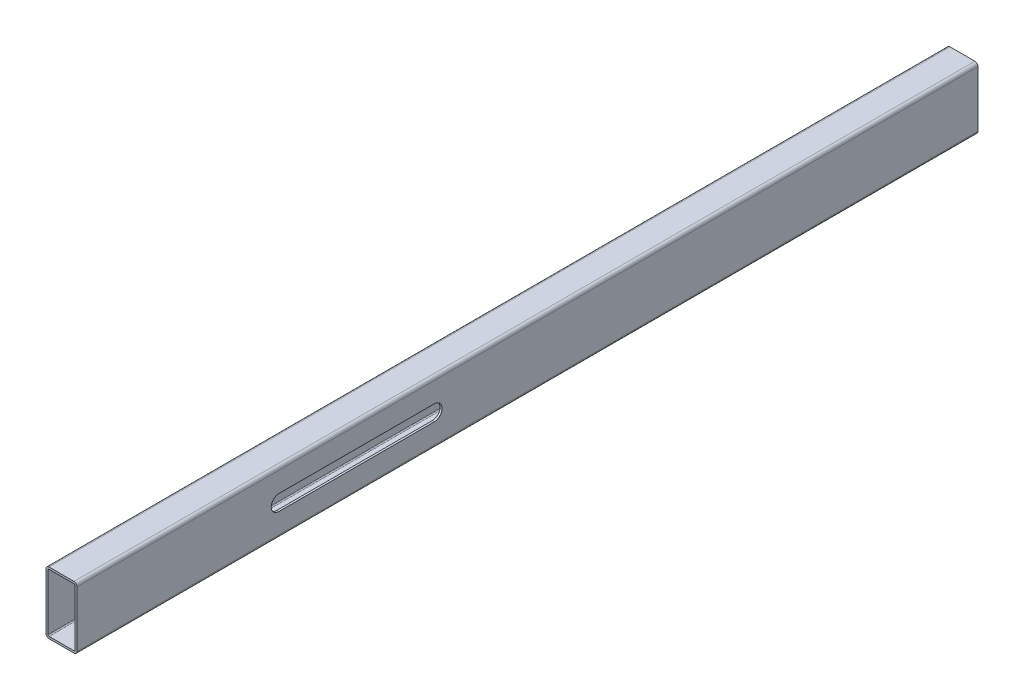
SolidWorks part; units mm, degrees
ref_plane "Front Plane" through (0, 0, 0) normal (0, 0, 1) x (1, 0, 0)
ref_plane "Top Plane" through (0, 0, 0) normal (0, 1, 0) x (1, 0, 0)
ref_plane "Right Plane" through (0, 0, 0) normal (1, 0, 0) x (0, 0, -1)
sketch "Sketch1" plane through (0, 0, 0) normal (0, 0, 1) x (1, 0, 0)
  line L1 (10.16, -25.4) -> (-10.16, -25.4)
  line L2 (12.7, -22.86) -> (12.7, 22.86)
  line L3 (10.16, 25.4) -> (-10.16, 25.4)
  line L4 (-12.7, -22.86) -> (-12.7, 22.86)
  line L5 (12.7, -25.4) -> (-12.7, 25.4) construction
  line L6 (12.7, 25.4) -> (-12.7, -25.4) construction
  arc A0 (-10.16, -25.4) -> (-12.7, -22.86) centre (-10.16, -22.86) cw
  arc A1 (10.16, -25.4) -> (12.7, -22.86) centre (10.16, -22.86) ccw
  arc A2 (12.7, 22.86) -> (10.16, 25.4) centre (10.16, 22.86) ccw
  arc A3 (-10.16, 25.4) -> (-12.7, 22.86) centre (-10.16, 22.86) ccw
  point P0 (0, 0)
  dimension "D3" = 2.54
  dimension "D1" = 25.4
  dimension "D2" = 50.8
extrude "Extrude-Thin1" add sketch "Sketch1" along normal blind 736.6 thin thin type one direction reverse wall 1.651
sketch "Sketch2" [suppressed] plane through (-12.7, 0, 0) normal (-1, 0, 0) x (0, 0, 1)
  line L0 (25.4, 0) -> (152.4, 0) construction
  line L1 (25.4, 6.35) -> (152.4, 6.35)
  line L2 (25.4, -6.35) -> (152.4, -6.35)
  line L3 (0, 22.86) -> (0, -22.86) construction
  arc A0 (25.4, 6.35) -> (25.4, -6.35) centre (25.4, 0) ccw
  arc A1 (152.4, -6.35) -> (152.4, 6.35) centre (152.4, 0) ccw
  point P3 (88.9, 0)
  dimension "D1" = 12.7
  dimension "D2" = 127
  dimension "D3" = 25.4
extrude "Cut-Extrude1" [suppressed] cut sketch "Sketch2" against normal through all
sketch "Sketch3" plane through (-12.7, 0, 0) normal (-1, 0, 0) x (0, 0, 1)
  line L0 (571.5, 0) -> (444.5, 0) construction
  line L1 (571.5, -6.35) -> (444.5, -6.35)
  line L2 (571.5, 6.35) -> (444.5, 6.35)
  line L3 (736.6, 22.86) -> (736.6, -22.86) construction
  arc A0 (571.5, -6.35) -> (571.5, 6.35) centre (571.5, 0) ccw
  arc A1 (444.5, 6.35) -> (444.5, -6.35) centre (444.5, 0) ccw
  point P3 (508, 0)
  dimension "D1" = 12.7
  dimension "D2" = 165.1
  dimension "D3" = 127
extrude "Cut-Extrude2" cut sketch "Sketch3" against normal through all
